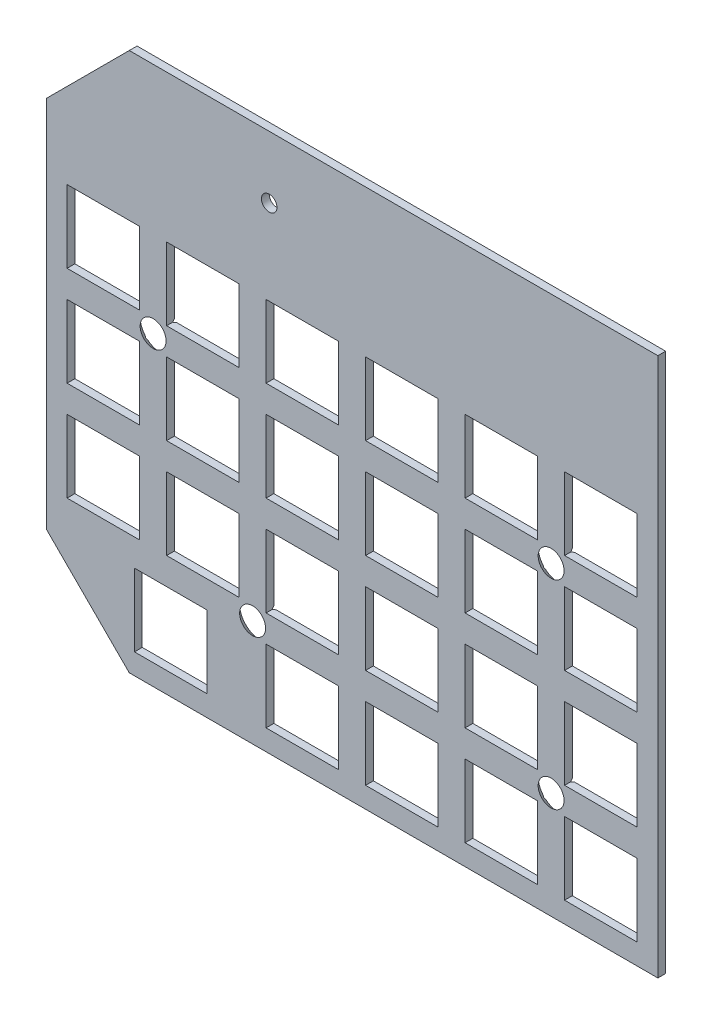
SolidWorks part; units mm, degrees
material "Alliage 1060"
ref_plane "Plan de face" through (0, 0, 0) normal (0, 0, 1) x (1, 0, 0)
ref_plane "Plan de dessus" through (0, 0, 0) normal (0, 1, 0) x (1, 0, 0)
ref_plane "Plan de droite" through (0, 0, 0) normal (1, 0, 0) x (0, 0, -1)
sketch "Esquisse1" plane through (0, 0, 0) normal (0, 0, 1) x (1, 0, 0)
  line L0 (0, -85) -> (16, -101)
  line L4 (118, 3) -> (118, -101)
  line L5 (16, 3) -> (0, -13)
  line L7 (118, 3) -> (16, 3)
  line L8 (0, -13) -> (0, -85)
  line L9 (16, -101) -> (118, -101)
  dimension "D1" = 104
  dimension "D2" = 118
  dimension "D3" = 16
  dimension "D4" = 16
  dimension "D5" = 16
  dimension "D6" = 16
extrude "Boss.-Extru.1" add sketch "Esquisse1" along normal blind 1.5
sketch "Esquisse3" plane through (0, 0, 0) normal (0, 0, -1) x (-1, 0, 0)
  line L0 (-94.8, -25.4) -> (-94.8, -39.4)
  line L1 (-114, -25.4) -> (-100, -25.4)
  line L2 (-114, -25.4) -> (-114, -39.4)
  line L3 (-114, -39.4) -> (-100, -39.4)
  line L4 (-100, -25.4) -> (-100, -39.4)
  line L5 (-107, -39.4) -> (-107, -25.4) construction
  line L6 (-114, -32.4) -> (-100, -32.4) construction
  line L7 (-94.8, -25.4) -> (-80.8, -25.4)
  line L8 (-80.8, -25.4) -> (-80.8, -39.4)
  line L9 (-94.8, -39.4) -> (-80.8, -39.4)
  line L10 (-75.6, -25.4) -> (-75.6, -39.4)
  line L11 (-75.6, -25.4) -> (-61.6, -25.4)
  line L12 (-61.6, -25.4) -> (-61.6, -39.4)
  line L13 (-75.6, -39.4) -> (-61.6, -39.4)
  line L14 (-56.4, -25.4) -> (-56.4, -39.4)
  line L15 (-56.4, -25.4) -> (-42.4, -25.4)
  line L16 (-42.4, -25.4) -> (-42.4, -39.4)
  line L17 (-56.4, -39.4) -> (-42.4, -39.4)
  line L18 (-37.2, -25.4) -> (-37.2, -39.4)
  line L19 (-37.2, -25.4) -> (-23.2, -25.4)
  line L20 (-23.2, -25.4) -> (-23.2, -39.4)
  line L21 (-37.2, -39.4) -> (-23.2, -39.4)
  line L22 (-18, -25.4) -> (-18, -39.4)
  line L23 (-18, -25.4) -> (-4, -25.4)
  line L24 (-4, -25.4) -> (-4, -39.4)
  line L25 (-18, -39.4) -> (-4, -39.4)
  line L26 (-94.8, -44.6) -> (-94.8, -58.6)
  line L27 (-94.8, -44.6) -> (-80.8, -44.6)
  line L28 (-80.8, -44.6) -> (-80.8, -58.6)
  line L29 (-94.8, -58.6) -> (-80.8, -58.6)
  line L30 (-75.6, -44.6) -> (-75.6, -58.6)
  line L31 (-75.6, -44.6) -> (-61.6, -44.6)
  line L32 (-61.6, -44.6) -> (-61.6, -58.6)
  line L33 (-75.6, -58.6) -> (-61.6, -58.6)
  line L34 (-56.4, -44.6) -> (-56.4, -58.6)
  line L35 (-56.4, -44.6) -> (-42.4, -44.6)
  line L36 (-42.4, -44.6) -> (-42.4, -58.6)
  line L37 (-56.4, -58.6) -> (-42.4, -58.6)
  line L38 (-37.2, -44.6) -> (-37.2, -58.6)
  line L39 (-37.2, -44.6) -> (-23.2, -44.6)
  line L40 (-23.2, -44.6) -> (-23.2, -58.6)
  line L41 (-37.2, -58.6) -> (-23.2, -58.6)
  line L42 (-18, -44.6) -> (-18, -58.6)
  line L43 (-18, -44.6) -> (-4, -44.6)
  line L44 (-4, -44.6) -> (-4, -58.6)
  line L45 (-18, -58.6) -> (-4, -58.6)
  line L46 (-94.8, -63.8) -> (-94.8, -77.8)
  line L47 (-94.8, -63.8) -> (-80.8, -63.8)
  line L48 (-80.8, -63.8) -> (-80.8, -77.8)
  line L49 (-94.8, -77.8) -> (-80.8, -77.8)
  line L50 (-75.6, -63.8) -> (-75.6, -77.8)
  line L51 (-75.6, -63.8) -> (-61.6, -63.8)
  line L52 (-61.6, -63.8) -> (-61.6, -77.8)
  line L53 (-75.6, -77.8) -> (-61.6, -77.8)
  line L54 (-56.4, -63.8) -> (-56.4, -77.8)
  line L55 (-56.4, -63.8) -> (-42.4, -63.8)
  line L56 (-42.4, -63.8) -> (-42.4, -77.8)
  line L57 (-56.4, -77.8) -> (-42.4, -77.8)
  line L58 (-37.2, -63.8) -> (-37.2, -77.8)
  line L59 (-37.2, -63.8) -> (-23.2, -63.8)
  line L60 (-23.2, -63.8) -> (-23.2, -77.8)
  line L61 (-37.2, -77.8) -> (-23.2, -77.8)
  line L62 (-18, -63.8) -> (-18, -77.8)
  line L63 (-18, -63.8) -> (-4, -63.8)
  line L64 (-4, -63.8) -> (-4, -77.8)
  line L65 (-18, -77.8) -> (-4, -77.8)
  line L66 (-94.8, -83) -> (-94.8, -97)
  line L67 (-94.8, -83) -> (-80.8, -83)
  line L68 (-80.8, -83) -> (-80.8, -97)
  line L69 (-94.8, -97) -> (-80.8, -97)
  line L70 (-75.6, -83) -> (-75.6, -97)
  line L71 (-75.6, -83) -> (-61.6, -83)
  line L72 (-61.6, -83) -> (-61.6, -97)
  line L73 (-75.6, -97) -> (-61.6, -97)
  line L74 (-56.4, -83) -> (-56.4, -97)
  line L75 (-56.4, -83) -> (-42.4, -83)
  line L76 (-42.4, -83) -> (-42.4, -97)
  line L77 (-56.4, -97) -> (-42.4, -97)
  line L86 (-114, -44.6) -> (-114, -58.6)
  line L87 (-114, -44.6) -> (-100, -44.6)
  line L88 (-100, -44.6) -> (-100, -58.6)
  line L89 (-114, -58.6) -> (-100, -58.6)
  line L90 (-114, -63.8) -> (-114, -77.8)
  line L91 (-114, -63.8) -> (-100, -63.8)
  line L92 (-100, -63.8) -> (-100, -77.8)
  line L93 (-114, -77.8) -> (-100, -77.8)
  line L94 (-114, -83) -> (-114, -97)
  line L95 (-114, -83) -> (-100, -83)
  line L96 (-100, -83) -> (-100, -97)
  line L97 (-114, -97) -> (-100, -97)
  line L98 (-4, -83) -> (-4, -97) [skipped]
  line L99 (-18, -97) -> (-4, -97) [skipped]
  line L100 (-18, -83) -> (-18, -97) [skipped]
  line L101 (-18, -83) -> (-4, -83) [skipped]
  line L103 (-118, -101) -> (-118, 3) construction
  line L104 (-16, -101) -> (-118, -101) construction
  line L107 (-37.2, -83) -> (-23.2, -83) [skipped]
  line L108 (-23.2, -83) -> (-23.2, -97) [skipped]
  line L109 (-37.2, -83) -> (-37.2, -97) [skipped]
  line L110 (-37.2, -97) -> (-23.2, -97) [skipped]
  line L111 (0, -13) -> (0, -85) construction
  line L112 (-31, -83) -> (-17, -83)
  line L113 (-31, -83) -> (-31, -97)
  line L114 (-31, -97) -> (-17, -97)
  line L115 (-17, -83) -> (-17, -97)
  line L116 (-24, -97) -> (-24, -83) construction
  line L117 (-31, -90) -> (-17, -90) construction
  line L122 (-118, 3) -> (-16, 3) construction
  circle A5 centre (-43, -9) radius 1.5
  point P0 (-107, -32.4)
  point P84 (-24, -90)
  dimension "D7" = 43
  dimension "D8" = 12
  dimension "D1" = 14
  dimension "D2" = 14
  dimension "D5" = 4
  dimension "D6" = 4
  dimension "D9" = 5.2
  dimension "D10" = 14
  dimension "D11" = 14
  dimension "D12" = 17
  dimension "D13" = 5.2
  dimension "D3" = 6
  dimension "D4" = 4
extrude "Enlèv. mat.-Extru.2" cut sketch "Esquisse3" against normal blind 10
sketch "Esquisse4" plane through (0, 0, 0) normal (0, 0, -1) x (-1, 0, 0)
  line L0 (-100, -39.4) -> (-94.8, -44.6) construction
  line L1 (-23.2, -39.4) -> (-18, -44.6) construction
  line L2 (-37.2, -77.8) -> (-42.4, -83) construction
  line L3 (-94.8, -77.8) -> (-100, -83) construction
  point P16 (-97.4, -42)
  point P17 (-97.4, -80.4)
  point P18 (-39.8, -80.4)
hole_wizard "Fraisage pour vis à tête fraisée M41" positions "Esquisse5" profile "Esquisse6" countersink size "M4" standard "Ansi Metric" end condition through all
sketch "Esquisse5" plane through (0, 0, 0) normal (0, 0, -1) x (-1, 0, 0)
  line L0 (-23.2, -39.4) -> (-18, -44.6) construction
  line L1 (-37.2, -77.8) -> (-42.4, -83) construction
  point P0 (-97.4, -42)
  point P3 (-97.4, -80.4)
  point P6 (-20.6, -42)
  point P10 (-39.8, -80.4)
sketch "Esquisse6" plane through (97.4, -42, 0) normal (1, 0, 0) x (0, 1, 0)
  line L0 (0, 0) -> (0, 1.5)
  line L1 (0, 1.5) -> (2.25, 1.5)
  line L2 (2.25, 1.5) -> (2.25, 1.75)
  line L3 (2.25, 1.75) -> (4, 0)
  line L5 (4, 0) -> (0, 0)
  line L6 (-2.25, 1.75) -> (-4, 0) construction
  line L11 (0, -6.35) -> (0, 107.95) construction
  dimension "Diamètre du perçage jusqu'au prochain" = 4.5
  dimension "Profondeur du perçage jusqu'au prochain" = 1.5
  dimension "Diamètre du fraisage entrant" = 8
  dimension "Angle du fraisage entrant" = 90
